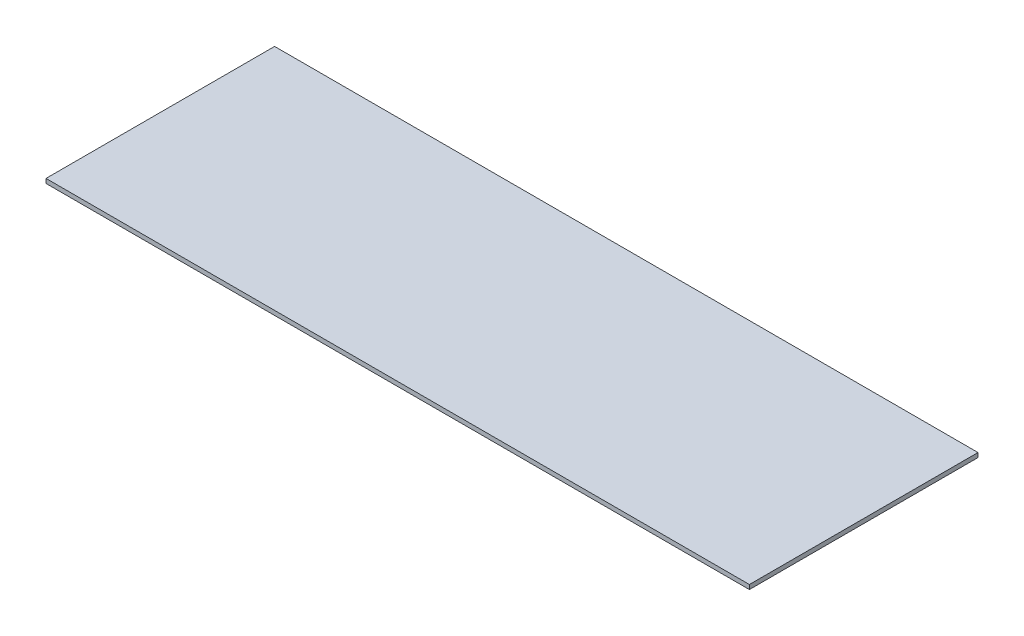
SolidWorks part; units mm, degrees
ref_plane "Front Plane" through (0, 0, 0) normal (0, 0, 1) x (1, 0, 0)
ref_plane "Top Plane" through (0, 0, 0) normal (0, 1, 0) x (1, 0, 0)
ref_plane "Right Plane" through (0, 0, 0) normal (1, 0, 0) x (0, 0, -1)
sketch "Sketch1" plane through (0, 0, 0) normal (0, 1, 0) x (1, 0, 0)
  line L1 (0, 0) -> (508, 0)
  line L2 (0, 0) -> (0, -165.1)
  line L3 (0, -165.1) -> (508, -165.1)
  line L4 (508, 0) -> (508, -165.1)
  dimension "D1" = 508
  dimension "D2" = 165.1
extrude "Boss-Extrude1" add sketch "Sketch1" along normal blind 3.175
